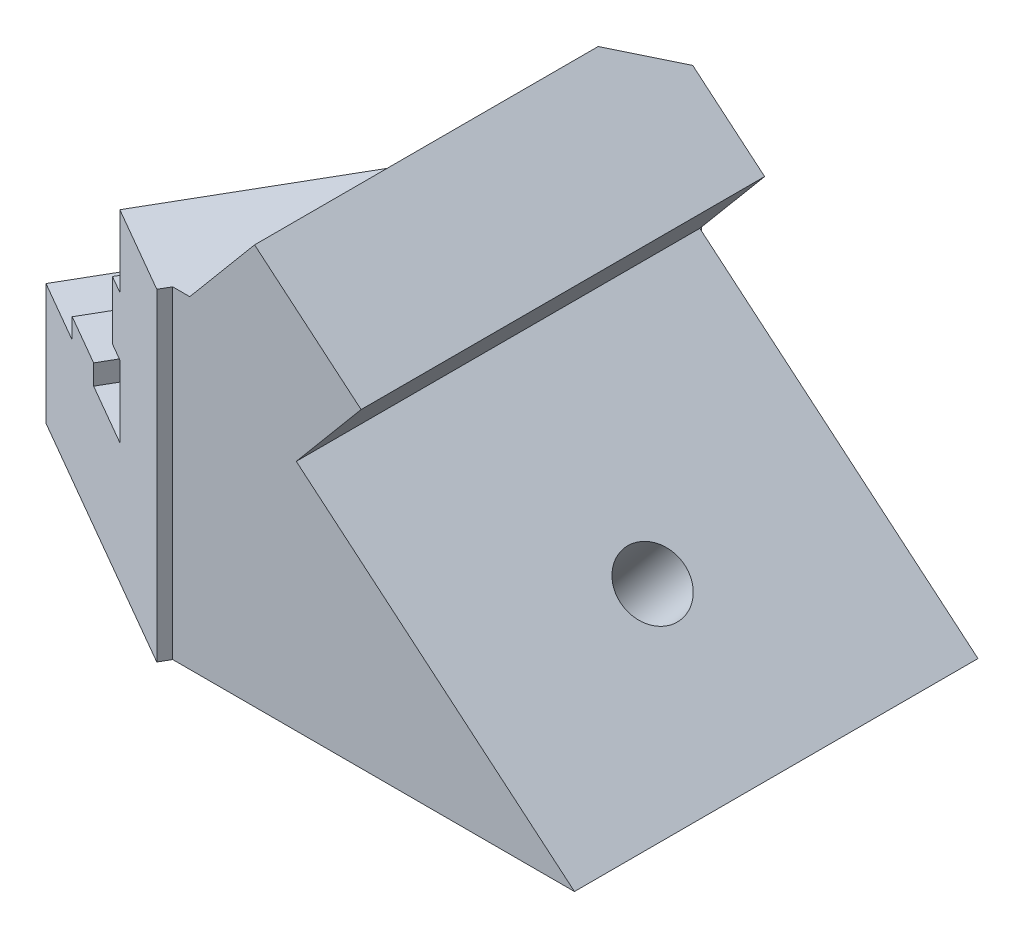
SolidWorks part; units mm, degrees
ref_plane "Front Plane" through (0, 0, 0) normal (0, 0, 1) x (1, 0, 0)
ref_plane "Top Plane" through (0, 0, 0) normal (0, 1, 0) x (1, 0, 0)
ref_plane "Right Plane" through (0, 0, 0) normal (1, 0, 0) x (0, 0, -1)
sketch "Esquisse1" plane through (0, 0, 0) normal (0, 0, 1) x (1, 0, 0)
  line L0 (2, 16) -> (21.0681, 0)
  line L1 (21.0681, 0) -> (0, 0)
  line L2 (0, 0) -> (0, 16)
  line L3 (0, 16) -> (2, 16)
  dimension "D1" = 2
  dimension "D2" = 140
  dimension "D3" = 16
extrude "Boss.-Extru.1" add sketch "Esquisse1" along normal blind 20
sketch "Esquisse2" plane through (8.7048, 10.374, 0) normal (0.6428, 0.766, 0) x (0, 0, -1)
  line L0 (-20, -16.1391) -> (0, -16.1391) construction
  line L3 (-20, -16.1391) -> (-20, 8.7525) construction
  circle A0 centre (-10, -8.1391) radius 1.6
  dimension "D1" = 3.2
  dimension "D2" = 8
  dimension "D3" = 10
extrude "HoleForLauncherFixing" cut sketch "Esquisse2" against normal through all
ref_plane "Plan1" through (5.4909, 6.5438, 0) normal (0.6428, 0.766, 0) x (0, 0, -1)
sketch "Esquisse3" plane through (5.4909, 6.5438, 0) normal (0.6428, 0.766, 0) x (0, 0, -1)
  circle A0 centre (-10, -8.1391) radius 4.25
  circle A1 centre (-10, -8.1391) radius 1.6 construction
  dimension "D1" = 8.5
extrude "BigHoleForLauncherFixing" cut sketch "Esquisse3" against normal through all
ref_axis "Axe1" through (3.9627, 7.8261, 0) along (0.766, -0.6428, 0)
ref_plane "Plan3" through (0, 0, 0) normal (-0.866, 0, -0.5) x (0, -1, 0)
sketch "Esquisse4" plane through (0, 0, 0) normal (-0.866, 0, -0.5) x (0, -1, 0)
  line L1 (4.4994, 17.8157) -> (-17.7877, 17.8157)
  line L2 (4.4994, 17.8157) -> (4.4994, -17.0003)
  line L3 (4.4994, -17.0003) -> (-17.7877, -17.0003)
  line L4 (-17.7877, 17.8157) -> (-17.7877, -17.0003)
extrude "Enlèv. mat.-Extru.3" cut sketch "Esquisse4" against normal blind 6
ref_plane "Plan4" through (1.7321, 0, -3) normal (-0.5, 0, 0.866) x (0, 1, 0)
ref_plane "Plan5" through (0, 0, 12) normal (0.5, 0, -0.866) x (-0.866, 0, -0.5)
ref_plane "Plan6" through (-8.6603, 0, 15) normal (0.5, 0, -0.866) x (-0.866, 0, -0.5)
sketch "Esquisse5" plane through (-3.4641, 0, 18) normal (0.5, 0, -0.866) x (-0.866, 0, -0.5)
  line L0 (-5, 0) -> (10, 0)
  line L1 (10, 0) -> (10, 6)
  line L2 (10, 6) -> (6.45, 6)
  line L3 (6.45, 6) -> (6.45, 7)
  line L4 (6.45, 7) -> (3.55, 7)
  line L5 (3.55, 7) -> (3.55, 6)
  line L6 (3.55, 6) -> (0, 6)
  line L7 (0, 6) -> (0, 9.55)
  line L8 (0, 9.55) -> (1, 9.55)
  line L9 (1, 9.55) -> (1, 12.45)
  line L10 (1, 12.45) -> (0, 12.45)
  line L11 (0, 12.45) -> (0, 16)
  line L12 (0, 16) -> (-5, 16)
  line L13 (-5, 16) -> (-5, 0)
  line L16 (0, 16) -> (0, 0) construction
  dimension "D1" = 10
  dimension "D2" = 2.9
  dimension "D3" = 1
  dimension "D4" = 6
  dimension "D5" = 5
  dimension "D6" = 10
extrude "MakerBeanFixing" add sketch "Esquisse5" along normal blind 21
sketch "Esquisse6" plane through (8.7048, 10.374, 0) normal (0.6428, 0.766, 0) x (0, 0, -1)
  line L0 (0, -16.1391) -> (0, 1.7569) construction
  line L1 (0, 1.8609) -> (-20, 1.8609)
  line L2 (0, 1.8609) -> (0, 8.7525)
  line L3 (0, 8.7525) -> (-20, 8.7525)
  line L4 (-20, 1.8609) -> (-20, 8.7525)
  line L5 (-20, -16.1391) -> (0, -16.1391) construction
  dimension "D1" = 18
extrude "Boss.-Extru.4" add sketch "Esquisse6" along normal blind 5
sketch "Esquisse7" plane through (0, 7, 0) normal (0, 1, 0) x (1, 0, 0)
  line L2 (1.45, 3.4115) -> (3.9615, 1.9615) construction
  line L3 (3.9615, 1.9615) -> (-6.5385, -16.225) construction
  circle A0 centre (-2.2942, -5.9737) radius 1.6
  dimension "D1" = 3.2
  dimension "D2" = 10
  dimension "D3" = 1.45
extrude "TopMakerBeanFixingHole" cut sketch "Esquisse7" against normal through all
sketch "Esquisse8" plane through (0, 0, 0) normal (0, 0, -1) x (-1, 0, 0)
  line L0 (-7.2793, 11.5702) -> (-21.0681, 0)
  line L1 (-21.0681, 0) -> (-7.359, 11.5033) construction
  line L2 (-21.0681, 0) -> (-26.2104, 6.1284)
  line L3 (-26.2104, 6.1284) -> (-7.1423, 22.1284)
  line L4 (-7.2793, 11.5702) -> (-10.4932, 15.4004)
  line L6 (-21.0681, 0) -> (-7.359, 11.5033) construction
  line L9 (-10.4932, 15.4004) -> (-5.2139, 19.8302)
  line L10 (-5.2139, 19.8302) -> (-7.1423, 22.1284)
  point P9 (-6.5607, 20.9203)
  dimension "D1" = 3
extrude "Enlèv. mat.-Extru.4" cut sketch "Esquisse8" against normal through all
sketch "Esquisse9" plane through (-3.4641, 0, 18) normal (0.5, 0, -0.866) x (-0.866, 0, -0.5)
  line L0 (0, 12.45) -> (0, 16) construction
  line L1 (0, 12.45) -> (8, 12.45)
  line L2 (0, 12.45) -> (0, 20.45)
  line L3 (0, 20.45) -> (8, 20.45)
  line L4 (8, 12.45) -> (8, 20.45)
  point P4 (2.863, 12.1108)
  point P5 (1.3699, 16.9598)
  point P7 (0, 12.3831)
  point P8 (0, 12.6665)
  point P9 (0, 12.45)
  point P12 (0, 17.7407)
  point P13 (0, 12.45)
  dimension "D1" = 8
  dimension "D2" = 8
extrude "Enlèv. mat.-Extru.6" cut sketch "Esquisse9" along normal through all
